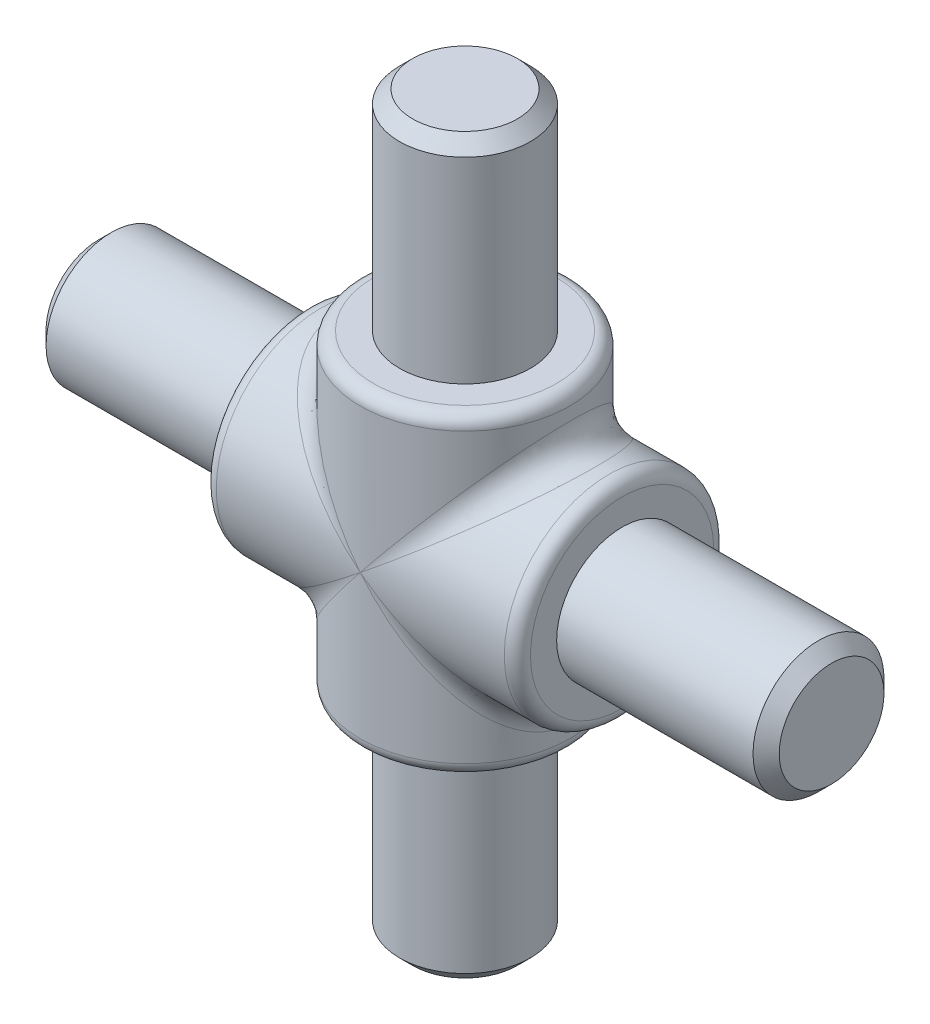
SolidWorks part; units mm, degrees
ref_plane "Front Plane" through (0, 0, 0) normal (0, 0, 1) x (1, 0, 0)
ref_plane "Top Plane" through (0, 0, 0) normal (0, 1, 0) x (1, 0, 0)
ref_plane "Right Plane" through (0, 0, 0) normal (1, 0, 0) x (0, 0, -1)
sketch "Sketch1" plane through (0, 0, 0) normal (0, 0, 1) x (1, 0, 0)
  line L0 (0, 0) -> (23.4828, 0) construction
  line L1 (8, 0) -> (8, 12)
  line L2 (8, 12) -> (5, 12)
  line L3 (5, 12) -> (5, 28)
  line L4 (5, 28) -> (0, 28)
  line L5 (0, 28) -> (0, 0)
  line L6 (8, 0) -> (0, 0)
  dimension "D1" = 5
  dimension "D2" = 8
  dimension "D3" = 28
  dimension "D4" = 16
revolve "Revolve1" add sketch "Sketch1" angle 360 about L5
fillet "Fillet2" radius 1 1 edges at (0, 12, 8)
chamfer "Chamfer1" distance 1 angle 45 1 edges at (0, 28, 5)
ref_axis "Axis1" through (0, 0, 8.8) along (0, 0, -1)
pattern_circular "CirPattern1" count 4 over 360 about axis through (0, 0, 8.8) along (0, 0, -1) of "Revolve1", "Fillet2", "Chamfer1"
fillet "Fillet1" radius 2 4 edges at (-8, 8, 0) (-8, -8, 0) (8, -8, 0) (8, 8, 0)
